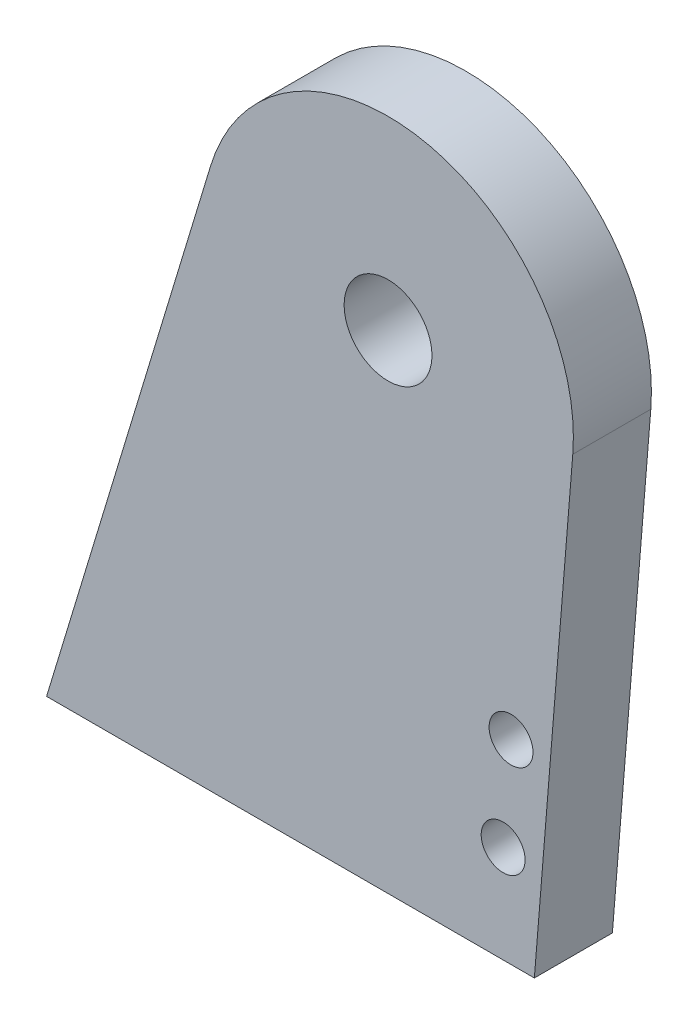
SolidWorks part; units mm, degrees
material "5052-O"
ref_plane "정면" through (0, 0, 0) normal (0, 0, 1) x (1, 0, 0)
ref_plane "윗면" through (0, 0, 0) normal (0, 1, 0) x (1, 0, 0)
ref_plane "우측면" through (0, 0, 0) normal (1, 0, 0) x (0, 0, -1)
sketch "스케치1" plane through (0, 0, 0) normal (0, 0, 1) x (1, 0, 0)
  line L0 (0, 0) -> (50, 0)
  line L1 (50, 0) -> (53.9376, 48.4613)
  line L2 (0, 0) -> (16.8161, 55.5087)
  circle A0 centre (35, 50) radius 19
  dimension "D1" = 38
  dimension "D2" = 50
  dimension "D3" = 50
  dimension "D5" = 15
extrude "보스-돌출1" add sketch "스케치1" along normal blind 8 contours A0 L2 L0 L1 | A0 region at (27.7427, 17.8369, 0) region at (35, 50, 0)
hole_wizard "M4 여유 구멍1" positions "스케치2" profile "스케치3" hole size "M4" standard "ISO" end condition up to next
sketch "스케치2" plane through (0, 0, 8) normal (0, 0, 1) x (1, 0, 0)
  line L0 (47.6092, 19.9672) -> (46.7993, 10)
  line L2 (50, 0) -> (53.9376, 48.4613) construction
  line L3 (0, 0) -> (50, 0) construction
  point P0 (46.7993, 10)
  point P2 (47.6092, 19.9672)
  dimension "D1" = 10
  dimension "D2" = 4
  dimension "D3" = 10
sketch "스케치3" plane through (46.7993, 10, 8) normal (1, 0, 0) x (0, -1, 0)
  line L0 (0, 0) -> (0, 8)
  line L1 (0, 8) -> (2.25, 8)
  line L2 (2.25, 8) -> (2.25, 0)
  line L5 (2.25, 0) -> (0, 0)
  line L11 (0, -6.35) -> (0, 107.95) construction
  dimension "관통 구멍 지름" = 4.5
  dimension "관통 구멍 깊이" = 8
hole_wizard "M3 나사 구멍1" positions "스케치4" profile "스케치5" tap size "M3" standard "ISO"
sketch "스케치4" plane through (0, 0, 0) normal (0, -1, 0) x (-1, 0, 0)
  line L0 (-10, -4) -> (-40, -4)
  line L2 (0, 0) -> (-50, 0) construction
  line L3 (-50, -8) -> (-50, 0) construction
  point P0 (-10, -4)
  point P2 (-40, -4)
  point P8 (-25, -4)
  point P11 (-25, 0)
  point P14 (-50, -4)
  dimension "D1" = 30
sketch "스케치5" plane through (10, 0, 4) normal (1, 0, 0) x (0, 0, -1)
  line L0 (0, 0) -> (0, 9.2511)
  line L1 (0, 9.2511) -> (1.25, 8.5)
  line L2 (1.25, 8.5) -> (1.25, 0.275)
  line L3 (1.25, 0.275) -> (1.525, 0)
  line L5 (1.525, 0) -> (0, 0)
  line L6 (-1.25, 0.275) -> (-1.525, 0) construction
  line L10 (0, 9.2511) -> (-1.25, 8.5) construction
  line L11 (0, -6.35) -> (0, 107.95) construction
  dimension "탭 드릴 지름" = 2.5
  dimension "탭 드릴 깊이" = 8.5
  dimension "표면 카운터싱크 지름" = 3.05
  dimension "표면 카운터싱크 각도" = 90
  dimension "드릴 각도" = 118
cosmetic thread "구멍 나사산1" parameters "D1"=6, "D2"=3
cosmetic thread "구멍 나사산2" parameters "D1"=6, "D2"=3
hole_wizard "M8 여유 구멍1" positions "스케치6" profile "스케치7" hole size "M8" standard "ISO" end condition through all
sketch "스케치6" plane through (0, 0, 0) normal (0, 0, -1) x (-1, 0, 0)
  point P0 (-35, 50)
sketch "스케치7" plane through (35, 50, 0) normal (1, 0, 0) x (0, 1, 0)
  line L0 (0, 0) -> (0, 8)
  line L1 (0, 8) -> (4.5, 8)
  line L2 (4.5, 8) -> (4.5, 0)
  line L5 (4.5, 0) -> (0, 0)
  line L11 (0, -6.35) -> (0, 107.95) construction
  dimension "관통 구멍 지름" = 9
  dimension "관통 구멍 깊이" = 8
